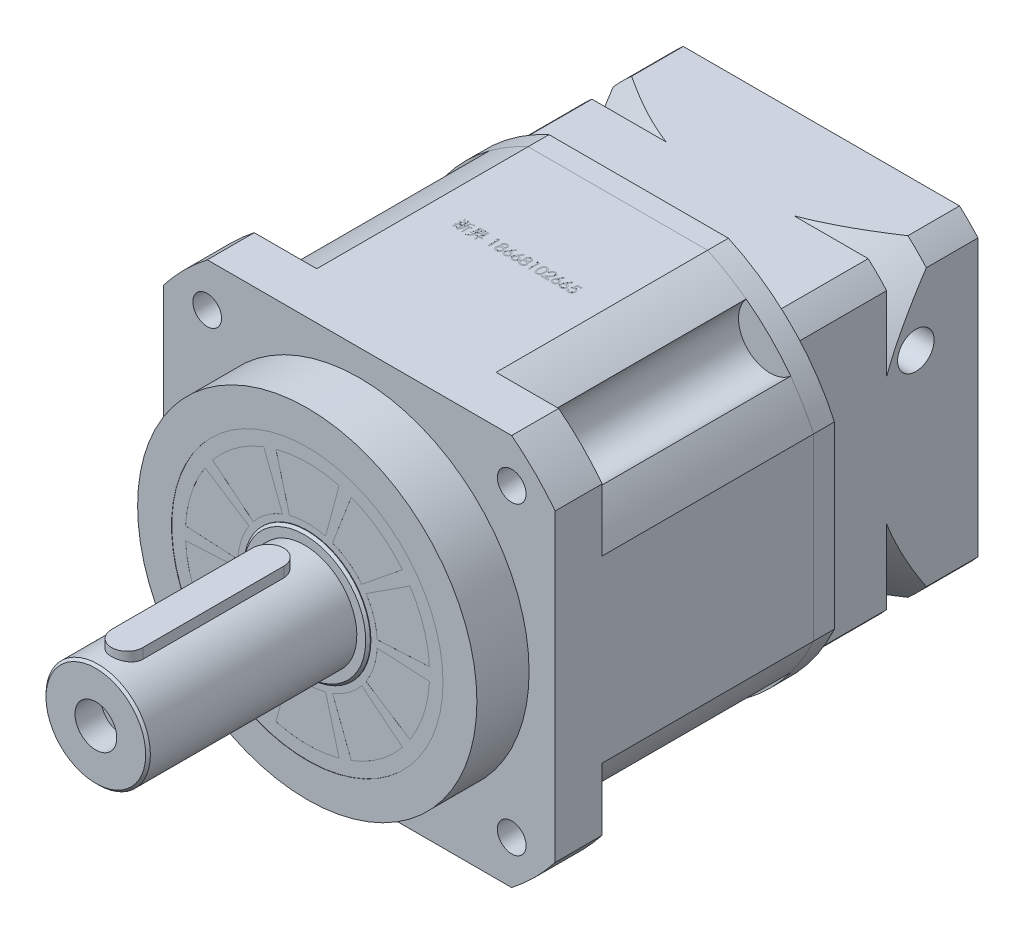
SolidWorks part; units mm, degrees
ref_plane "前视基准面" through (0, 0, 0) normal (0, 0, 1) x (1, 0, 0)
ref_plane "上视基准面" through (0, 0, 0) normal (0, 1, 0) x (1, 0, 0)
ref_plane "右视基准面" through (0, 0, 0) normal (1, 0, 0) x (0, 0, -1)
sketch "草图1" plane through (0, 0, 0) normal (1, 0, 0) x (0, 0, -1)
  line L0 (-139, 0) -> (139, 0) construction
  line L1 (139, 0) -> (139, 75)
  line L2 (139, 75) -> (-38, 75)
  line L3 (-38, 75) -> (-38, 65)
  line L4 (-38, 65) -> (-58, 65)
  line L5 (-58, 65) -> (-58, 24.3)
  line L6 (-58, 24.3) -> (-59, 24.3)
  line L7 (-59, 24.3) -> (-59, 20)
  line L8 (-59, 20) -> (-139, 20)
  line L9 (-139, 20) -> (-139, 0)
  line L10 (139, 55) -> (133, 55)
  line L11 (133, 55) -> (133, 11)
  line L12 (133, 11) -> (75.5, 11)
  line L13 (75.5, 11) -> (75.5, 0)
  line L14 (139, 44) -> (91.375, 44)
  line L15 (91.375, 44) -> (91.375, 0)
  line L16 (115.1875, 44) -> (115.1875, 0) construction
  line L17 (139, 44) -> (133, 11) construction
  line L18 (136, 27.5) -> (91.375, 27.5) construction
  point P3 (-20, 75)
  point P12 (-133, 20)
  point P13 (-67, 20)
  point P14 (75.5, 0)
  point P15 (133, 0)
  point P18 (69, 75)
  point P22 (104, 75)
  point P30 (115.1875, 27.5)
  point P31 (115.1875, -27.5)
  point P32 (-59, 0)
  point P33 (21, 0)
  point P34 (11, 0)
  point P35 (132.5, 0)
  point P36 (89, 0)
  point P37 (61, 75)
  dimension "D1" = 150
  dimension "A" = 278
  dimension "D2" = 18
  dimension "D3" = 20
  dimension "D4" = 80
  dimension "D5" = 66
  dimension "D6" = 6
  dimension "D7" = 40
  dimension "D8" = 48.6
  dimension "D9" = 130
  dimension "D10" = 101
  dimension "D11" = 50
  dimension "C" = 63.5
  dimension "D12" = 6
  dimension "D13" = 110
  dimension "D14" = 22
  dimension "D15" = 70
  dimension "D16" = 35
  dimension "D17" = 47.625
  dimension "D18" = 88
  dimension "D19" = 21
  dimension "D20" = 80
  dimension "D21" = 10
  dimension "D22" = 6.5
  dimension "D23" = 8
sketch "草图2" plane through (0, 0, 0) normal (0, 0, 1) x (1, 0, 0)
  line L0 (0, 0) -> (0, 75) construction
  line L1 (-75, 75) -> (75, 75)
  line L2 (-75, 75) -> (-75, -75)
  line L3 (-75, -75) -> (75, -75)
  line L4 (75, 75) -> (75, -75)
  line L5 (0, 0) -> (75, 0) construction
  line L6 (-6, 23) -> (6, 23)
  line L7 (6, 23) -> (6, 19.0788)
  line L8 (-6, 23) -> (-6, 19.0788)
  line L9 (0, 0) -> (58.3363, 58.3363) construction
  line L10 (0, 0) -> (-51.2652, 51.2652) construction
  line L12 (-60, 60) -> (60, 60)
  line L13 (-60, 60) -> (-60, -60)
  line L14 (-60, -60) -> (60, -60)
  line L15 (60, 60) -> (60, -60)
  circle A0 centre (0, 0) radius 20
  circle A1 centre (0, 0) radius 8
  circle A2 centre (0, 0) radius 82.5 construction
  circle A3 centre (58.3363, 58.3363) radius 5.5
  circle A4 centre (0, 0) radius 95
  circle A5 centre (-51.2652, 51.2652) radius 4
  circle A7 centre (58.3363, 58.3363) radius 12.1
  circle A8 centre (0, 0) radius 72.5 construction
  point P13 (0, -20)
  dimension "D2" = 12
  dimension "D4" = 16
  dimension "D5" = 165
  dimension "D7" = 11
  dimension "D8" = 190
  dimension "D9" = 8
  dimension "D11" = 24.2
  dimension "D12" = 145
  dimension "D1" = 150
  dimension "D3" = 43
  dimension "D6" = 45
  dimension "D10" = 45
  dimension "B" = 120
sketch "草图3" plane through (0, 0, 0) normal (0, 0, 1) x (1, 0, 0)
  line L0 (-75, 75) -> (75, 75) construction
  line L1 (-75, 75) -> (-75, -75) construction
  line L2 (-75, -75) -> (75, -75) construction
  line L3 (75, 75) -> (75, -75) construction
  line L4 (-75, 75) -> (75, 75)
  line L5 (-75, 75) -> (-75, -75)
  line L6 (-75, -75) -> (75, -75)
  line L7 (75, 75) -> (75, -75)
extrude "凸台-拉伸1" add sketch "草图3" along normal up to vertex (38 mm away) from vertex up to point (0, 75, 38) starting at point (0, 75, -69)
sketch "草图33" plane through (0, 0, 0) normal (0, 0, 1) x (1, 0, 0)
  line L0 (-60, 60) -> (-60, -60) construction
  line L1 (-60, -60) -> (60, -60) construction
  line L2 (60, 60) -> (60, -60) construction
  line L3 (-60, 60) -> (60, 60) construction
  line L4 (-60, 60) -> (-60, -60)
  line L5 (-60, -60) -> (60, -60)
  line L6 (60, 60) -> (60, -60)
  line L7 (-60, 60) -> (60, 60)
extrude "凸台-拉伸7" add sketch "草图33" along normal up to vertex (-69 mm away) from vertex up to point (0, 75, -69) starting at point (0, 75, -139)
sketch "草图4" plane through (0, 0, 0) normal (1, 0, 0) x (0, 0, -1)
  line L0 (-38, 65) -> (-58, 65) construction
  line L1 (-38, 65) -> (-58, 65)
  line L2 (-58, 65) -> (-58, 0)
  line L3 (-139, 0) -> (139, 0) construction
  line L4 (-58, 0) -> (-38, 0)
  line L5 (-38, 0) -> (-38, 65)
revolve "旋转1" add sketch "草图4" angle 360 about L4
sketch "草图5" plane through (0, 0, 58) normal (0, 0, 1) x (1, 0, 0)
  circle A0 centre (0, 0) radius 52
  dimension "D1" = 104
extrude "切除-拉伸1" cut sketch "草图5" against normal blind 0.1
sketch "草图6" plane through (0, 0, 0) normal (1, 0, 0) x (0, 0, -1)
  line L0 (-139, 20) -> (-139, 0) construction
  line L1 (-59, 20) -> (-139, 20) construction
  line L2 (-59, 24.3) -> (-59, 20) construction
  line L3 (-139, 20) -> (-139, 0)
  line L4 (-59, 20) -> (-139, 20)
  line L5 (-59, 24.3) -> (-59, 20)
  line L6 (-59, 24.3) -> (-38, 24.3)
  line L7 (-38, -75) -> (-38, 75) construction
  line L8 (-139, 0) -> (-38, 0)
  line L9 (-139, 0) -> (139, 0) construction
  line L10 (-38, 0) -> (-38, 24.3)
revolve "旋转2" add sketch "草图6" angle 360 about L8
sketch "草图13" plane through (0, 0, 139) normal (0, 0, 1) x (1, 0, 0)
  circle A0 centre (0, 0) radius 8 construction
  circle A1 centre (0, 0) radius 8
extrude "切除-拉伸7" cut sketch "草图13" against normal blind 10
cosmetic thread "装饰螺纹线1" parameters "D2"=16.1
sketch "草图8" plane through (0, 0, 0) normal (0, 1, 0) x (1, 0, 0)
  line L1 (-6, -73) -> (6, -73) construction
  line L2 (-6, -73) -> (-6, -127)
  line L3 (-6, -127) -> (6, -127) construction
  line L4 (6, -73) -> (6, -127)
  arc A0 (6, -73) -> (-6, -73) centre (0, -73) ccw
  arc A1 (-6, -127) -> (6, -127) centre (0, -127) ccw
  point P5 (0, -67)
  point P7 (0, -133)
extrude "凸台-拉伸2" add sketch "草图8" against normal up to vertex (-19.0788 mm away) from vertex up to point (6, 19.0788, 0) starting at point (6, 23, 0)
chamfer "倒角1" distance 0.9 angle 45 2 edges at (0, -24.3, 59) (0, -20, 139)
sketch "草图7" plane through (0, 0, 57.9) normal (0, 0, 1) x (1, 0, 0)
  line L0 (-6.9182, 25.8192) -> (-12.1127, 45.2053)
  line L1 (6.9182, 25.8192) -> (12.1127, 45.2053)
  line L2 (0, 20) -> (0, 0) construction
  arc A0 (12.1127, 45.2053) -> (-12.1127, 45.2053) centre (0, 0) ccw
  arc A1 (6.9182, 25.8192) -> (-6.9182, 25.8192) centre (0, 0) ccw
  dimension "D1" = 53.46
  dimension "D2" = 93.6
  dimension "D3" = 30
  dimension "D4" = 15
extrude "切除-拉伸2" cut sketch "草图7" against normal blind 0.01
pattern_circular "阵列(圆周)1" count 10 over 360 about axis through (0, 0, 58) along (0, 0, 1) of "切除-拉伸2"
sketch "草图9" plane through (0, 0, 0) normal (0, 0, 1) x (1, 0, 0)
  circle A1 centre (0, 0) radius 82.5 construction
  circle A2 centre (0, 0) radius 82.5
extrude "切除-拉伸3" cut sketch "草图9" along normal up to vertex (20 mm away) from vertex flip side to cut up to point (0, 75, 20) starting at point (0, 75, -104)
sketch "草图10" plane through (0, 0, 0) normal (0, 0, 1) x (1, 0, 0)
  circle A0 centre (58.3363, 58.3363) radius 12.1 construction
  circle A1 centre (58.3363, 58.3363) radius 12.1
extrude "切除-拉伸4" cut sketch "草图10" along normal up to vertex (20 mm away) from vertex up to point (0, 75, 20) starting at point (0, 75, -61)
sketch "草图11" plane through (0, 0, 0) normal (0, 0, 1) x (1, 0, 0)
  circle A0 centre (58.3363, 58.3363) radius 5.5 construction
  circle A1 centre (58.3363, 58.3363) radius 5.5
extrude "切除-拉伸5" cut sketch "草图11" along normal up to vertex (38 mm away) from vertex up to point (0, 75, 38) starting at point (0, 75, 20)
pattern_circular "阵列(圆周)2" count 4 over 360 about axis through (0, 0, 58) along (0, 0, 1) of "切除-拉伸4", "切除-拉伸5"
sketch "草图12" plane through (0, 0, 0) normal (0, 0, 1) x (1, 0, 0)
  circle A0 centre (0, 0) radius 95 construction
  circle A1 centre (0, 0) radius 95
extrude "切除-拉伸6" cut sketch "草图12" along normal up to vertex (38 mm away) from vertex flip side to cut up to point (0, 75, 38) starting at point (0, 75, -69)
sketch "草图34" plane through (0, 0, 0) normal (0, 0, 1) x (1, 0, 0)
  circle A0 centre (0, 0) radius 80
  dimension "D1" = 160
extrude "切除-拉伸13" cut sketch "草图34" along normal up to vertex (-69 mm away) from vertex flip side to cut up to point (0, 75, -69) starting at point (-60, 60, -139)
sketch "草图14" plane through (0, 0, -139) normal (0, 0, -1) x (-1, 0, 0)
  circle A0 centre (51.2652, 51.2652) radius 4 construction
  circle A1 centre (51.2652, 51.2652) radius 4
extrude "切除-拉伸8" cut sketch "草图14" against normal blind 10
cosmetic thread "装饰螺纹线2" parameters "D2"=8.1
pattern_circular "阵列(圆周)3" count 4 over 360 about axis through (0, 0, 58) along (0, 0, 1) of "切除-拉伸8"
sketch "草图15" plane through (0, 0, 0) normal (1, 0, 0) x (0, 0, -1)
  line L4 (139, 55) -> (91.375, 55)
  line L5 (91.375, 55) -> (91.375, 0)
  line L6 (91.375, 0) -> (139, 0)
  line L9 (139, 0) -> (139, 55)
revolve "切除-旋转1" cut sketch "草图15" angle 360 about L6
sketch "草图17" plane through (0, 0, -91.375) normal (0, 0, -1) x (-1, 0, 0)
  line L0 (0, 39.5505) -> (0, -39.6) construction
  line L1 (-1.98, 39.5505) -> (-1.98, -39.5505)
  line L2 (1.98, 39.5505) -> (1.98, -39.5505)
  line L3 (-28.494, 27.5) -> (28.494, 27.5) construction
  arc A0 (-1.98, 39.5505) -> (-1.98, -39.5505) centre (0, 0) ccw
  arc A1 (1.98, -39.5505) -> (1.98, 39.5505) centre (0, 0) ccw
  dimension "D1" = 79.2
  dimension "D2" = 3.96
extrude "凸台-拉伸3" add sketch "草图17" along normal up to vertex (41.125 mm away) up to point (0, 0, -132.5)
sketch "草图19" plane through (0, 0, 0) normal (1, 0, 0) x (0, 0, -1)
  line L0 (75.5, 11) -> (75.5, 0) construction
  line L1 (75.5, 11) -> (75.5, 0)
  line L2 (75.5, 11) -> (139, 11)
  line L3 (139, 0) -> (139, 75) construction
  line L4 (139, 11) -> (139, 0)
  line L5 (139, 0) -> (75.5, 0)
revolve "切除-旋转3" cut sketch "草图19" angle 360 about L5
sketch "草图26" plane through (0, 0, 0) normal (1, 0, 0) x (0, 0, -1)
  line L0 (133, 44) -> (133, 55)
  line L1 (133, 55) -> (133, 11) construction
  line L2 (139, 44) -> (91.375, 44) construction
  line L3 (133, 55) -> (91.375, 55)
  line L4 (91.375, 55) -> (91.375, 44)
  line L5 (91.375, 44) -> (133, 44)
  line L6 (-139, 0) -> (139, 0) construction
  line L7 (-139, 0) -> (139, 0) construction
revolve "旋转3" add sketch "草图26" angle 360 about L7
sketch "草图20" plane through (0, 0, 0) normal (1, 0, 0) x (0, 0, -1)
  circle A0 centre (115.1875, 27.5) radius 7
  dimension "D1" = 14
extrude "切除-拉伸9" cut sketch "草图20" against normal blind 10 and the other way through all from vertex starting at point (28.494, 27.5, -91.375)
sketch "草图25" plane through (0, 0, 0) normal (1, 0, 0) x (0, 0, -1)
  circle A0 centre (115.1875, -27.5) radius 7
  circle A1 centre (115.1875, 27.5) radius 7 construction
extrude "切除-拉伸11" cut sketch "草图25" against normal through all and the other way blind 10 from vertex starting at point (-28.494, 27.5, -91.375)
sketch "螺钉草图1" plane through (18.494, 15.4199, -49.0441) normal (1, 0, 0) x (0, 0, -1)
  circle A0 centre (66.1434, 12.0801) radius 6.65
  dimension "D1" = 13.3
extrude "拉伸-螺钉(内六角)" add sketch "螺钉草图1" along normal blind 7.98
fillet "圆角-螺钉(内六角)" radius 0.4433 1 edges at (26.474, 27.5, -121.8375)
sketch "螺钉草图2" plane through (26.474, 13.5, -50.375) normal (1, 0, 0) x (0, 0, -1)
  line L1 (69.4198, 14) -> (67.1161, 17.99)
  line L2 (67.1161, 17.99) -> (62.5089, 17.99)
  line L3 (62.5089, 17.99) -> (60.2052, 14)
  line L4 (60.2052, 14) -> (62.5089, 10.01)
  line L5 (62.5089, 10.01) -> (67.1161, 10.01)
  line L6 (67.1161, 10.01) -> (69.4198, 14)
  circle A0 centre (64.8125, 14) radius 3.99 construction
  dimension "D1" = 7.98
extrude "切除-螺钉(内六角)" cut sketch "螺钉草图2" against normal blind 4.655
sketch "草图23" plane through (0, 0, 0) normal (1, 0, 0) x (0, 0, -1)
  circle A0 centre (115.1875, 27.5) radius 4.9
  dimension "D1" = 9.8
extrude "凸台-拉伸5" add sketch "草图23" along normal mid plane 3.96
pattern_circular "阵列(圆周)4" count 2 over 360 about axis through (0, 0, 58) along (0, 0, 1) of "拉伸-螺钉(内六角)", "圆角-螺钉(内六角)", "切除-螺钉(内六角)", "凸台-拉伸5"
sketch "草图27" plane through (0, 0, 0) normal (1, 0, 0) x (0, 0, -1)
  line L0 (104, 64.8) -> (104, 164.8)
  line L1 (104, 164.8) -> (204, 164.8)
  line L2 (204, 164.8) -> (104, 64.8)
  line L3 (-139, 0) -> (139, 0) construction
  line L4 (-139, 0) -> (139, 0) construction
  dimension "D1" = 100
  dimension "D2" = 45
  dimension "D3" = 129.6
revolve "切除-旋转4" cut sketch "草图27" angle 360 about L4
sketch "草图28" plane through (0, 0, 0) normal (1, 0, 0) x (0, 0, -1)
  line L0 (61, 75) -> (61, -75)
  line L2 (69, -75) -> (-20, -75) construction
split line "分割线1"
sketch "孔输出草图1" plane through (0, 0, 0) normal (0, 0, 1) x (1, 0, 0)
  line L0 (0, 0) -> (0, 20) construction
  line L1 (-6, 23.3) -> (6, 23.3)
  line L2 (6, 23.3) -> (6, 19.0788)
  line L3 (-6, 23.3) -> (-6, 19.0788)
  circle A0 centre (0, 0) radius 20
  circle A1 centre (0, 0) radius 29.125
  point P7 (0, -20)
  dimension "D1" = 40
  dimension "D4" = 58.25
  dimension "D2" = 12
  dimension "D3" = 43.3
sketch "草图30" [suppressed] plane through (0, 0, 0) normal (0, 0, 1) x (1, 0, 0)
  circle A0 centre (0, 0) radius 29.125 construction
  circle A1 centre (0, 0) radius 29.125
extrude "凸台-拉伸6" [suppressed] add sketch "草图30" along normal up to vertex
sketch "草图31" [suppressed] plane through (0, 0, 59) normal (0, 0, 1) x (1, 0, 0)
  line L0 (-6, 23.3) -> (-6, 19.0788) construction
  line L1 (-6, 23.3) -> (6, 23.3) construction
  line L2 (6, 23.3) -> (6, 19.0788) construction
  line L3 (-6, 23.3) -> (-6, 19.0788)
  line L4 (-6, 23.3) -> (6, 23.3)
  line L5 (6, 23.3) -> (6, 19.0788)
  circle A0 centre (0, 0) radius 20 construction
  arc A1 (-6, 19.0788) -> (6, 19.0788) centre (0, 0) ccw
extrude "切除-拉伸12" [suppressed] cut sketch "草图31" against normal up to vertex
chamfer "倒角2" [suppressed] distance 1.0825 angle 45
sketch "草图32" [suppressed] plane through (0, 0, 0) normal (1, 0, 0) x (0, 0, -1)
  line L0 (11, 0) -> (11, 14)
  line L1 (11, 14) -> (21, 14)
  line L2 (21, 14) -> (21, 0)
  line L3 (21, 0) -> (11, 0)
  line L4 (-139, 0) -> (139, 0) construction
  line L5 (-139, 0) -> (139, 0) construction
  dimension "D1" = 28
revolve "切除-旋转5" [suppressed] cut sketch "草图32" angle 360 about L5
sketch "草图36" plane through (0, 0, -75.5) normal (0, 0, -1) x (-1, 0, 0)
  circle A0 centre (0, 0) radius 11.5
  dimension "D1" = 23
extrude "切除-拉伸14" cut sketch "草图36" along normal blind 10
sketch "草图37" plane through (0, 75, 0) normal (0, 1, 0) x (1, 0, 0)
  line L0 (-34.3693, 20.5) -> (34.3693, 20.5) construction
  line L1 (-34.3693, 61) -> (-34.3693, -20) construction
  line L2 (34.3693, -20) -> (34.3693, 61) construction
  text T0 "浙昇 18668102665" font "Century Gothic" height 4
extrude "LOGO" cut sketch "草图37" against normal blind 0.01
equation "\"D8@草图1\" = \"D7@草图1\" * 1.14+3"
equation "\"D1@草图5\" = \"D9@草图1\" * 0.8"
equation "\"D1@草图7\" = \"D8@草图1\" * 1.1"
equation "\"D2@草图7\" = \"D1@草图5\" * 0.9"
equation "\"D1@倒角1\" = \"D7@草图1\" / 100+0.5"
equation "\"D15@草图1\" =70"
equation "\"D1@草图2\" = \"D1@草图1\""
equation "\"D11@草图2\" = \"D7@草图2\" * 2.2"
equation "\"D2@装饰螺纹线1\" = \"D4@草图2\" + 0.1"
equation "\"D2@装饰螺纹线2\" = \"D9@草图2\" + 0.1"
equation "\"D17@草图1\" = \"C@草图1\" * 0.75"
equation "\"D18@草图1\" = \"D13@草图1\" * 0.8"
equation "\"D1@草图17\" = \"D18@草图1\" * 0.9"
equation "\"D2@草图17\" = \"D1@草图17\" * 0.05"
equation "\"D1@螺钉草图1\" = \"D1@草图20\" * 0.95"
equation "\"D1@拉伸-螺钉(内六角)\" = \"D1@螺钉草图1\"*0.6"
equation "\"D1@圆角-螺钉(内六角)\" = \"D1@螺钉草图1\"/30"
equation "\"D1@螺钉草图2\" = \"D1@螺钉草图1\"*0.6"
equation "\"D1@切除-螺钉(内六角)\" = \"D1@螺钉草图1\"*0.35"
equation "\"D1@草图23\" = \"D1@草图20\" * 0.7"
equation "\"D1@凸台-拉伸5\" = \"D2@草图17\""
equation "\"D3@草图27\" = \"B@草图2\" * 1.08"
equation "\"D4@孔输出草图1\" = ( \"D3@孔输出草图1\" - \"D1@孔输出草图1\" * 0.5 )  * 2*1.25"
equation "\"D1@倒角2\" = \"D4@孔输出草图1\"/100+0.5"
equation "\"D1@草图34\" =160"
